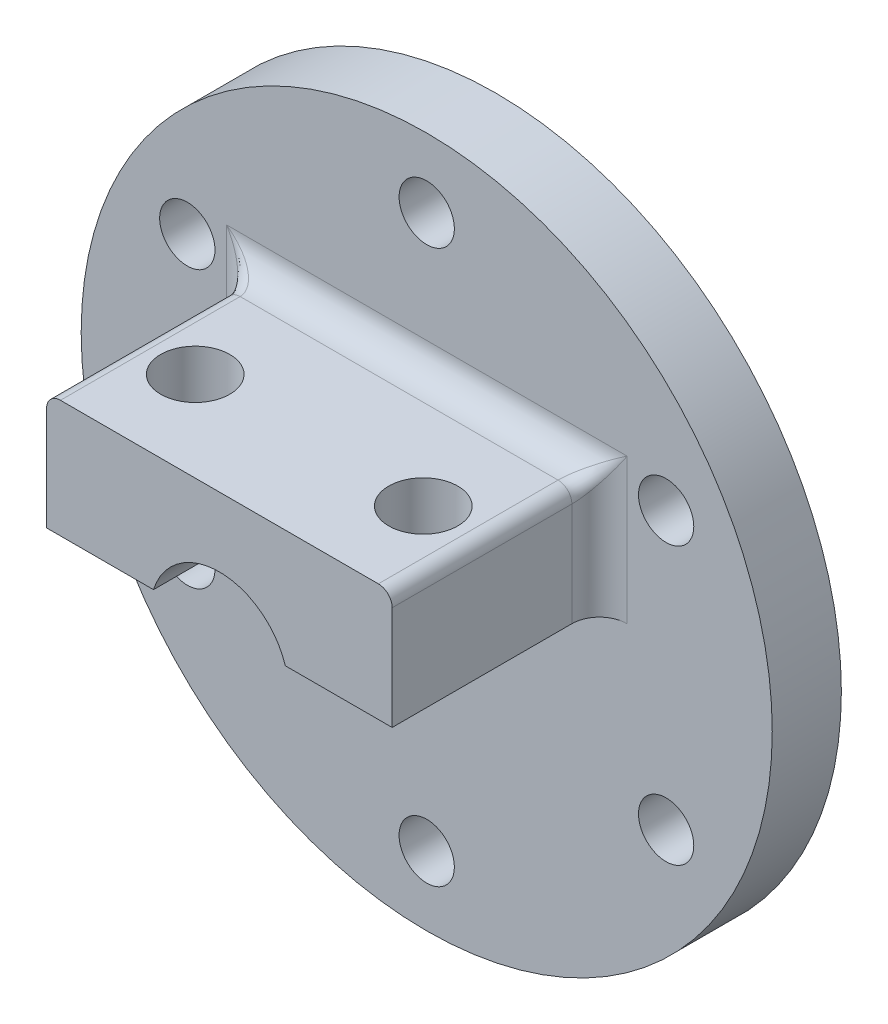
SolidWorks part; units mm, degrees
material "6061 合金"
ref_plane "前视基准面" through (0, 0, 0) normal (0, 0, 1) x (1, 0, 0)
ref_plane "上视基准面" through (0, 0, 0) normal (0, 1, 0) x (1, 0, 0)
ref_plane "右视基准面" through (0, 0, 0) normal (1, 0, 0) x (0, 0, -1)
other "Configuration Table"
sketch "草图2" plane through (0, 0, 0) normal (0, 0, 1) x (1, 0, 0)
  line L0 (0, 0) -> (0, 20)
  line L2 (-3, -4) -> (3, -4)
  circle A0 centre (0, 0) radius 25
  circle A2 centre (0, 20) radius 2
  circle A3 centre (17.3205, 10) radius 2
  circle A4 centre (17.3205, -10) radius 2
  circle A5 centre (0, -20) radius 2
  circle A6 centre (-17.3205, -10) radius 2
  circle A7 centre (-17.3205, 10) radius 2
  arc A8 (3, -4) -> (-3, -4) centre (0, 0) ccw
  point P18 (0, 0)
  dimension "D1" = 50
  dimension "D2" = 6
  dimension "D3" = 20
extrude "凸台-拉伸1" add sketch "草图2" along normal mid plane 5 contours A0 A7 A6 A5 A4 A3 A2 region at (-24.2929, 0, 0)
sketch "草图3" plane through (0, 0, 2.5) normal (0, 0, 1) x (1, 0, 0)
  line L0 (0, 0) -> (0, 10) construction
  line L1 (-12.5, 10) -> (12.5, 10)
  line L2 (-12.5, 10) -> (-12.5, 0)
  line L4 (12.5, 10) -> (12.5, 0)
  line L5 (-5, 0) -> (-12.5, 0)
  line L6 (-12.5, 0) -> (12.5, 0) construction
  line L7 (5, 0) -> (12.5, 0)
  arc A0 (5, 0) -> (-5, 0) centre (0, 0) ccw
  point P0 (0, 0)
  dimension "D1" = 25
  dimension "D2" = 10
extrude "凸台-拉伸2" add sketch "草图3" along normal blind 15
fillet "圆角1" radius 2 3 edges at (12.5, 5, 2.5) (0, 10, 2.5) (-12.5, 5, 2.5)
fillet "圆角2" radius 1 4 edges at (12.5, 10, 11) (-12.5, 10, 11) (13.0858, 10.5858, 3.0858) (-13.0858, 10.5858, 3.0858)
sketch "草图9" plane through (0, 10, 0) normal (0, 1, 0) x (1, 0, 0)
  line L0 (0, -4.5) -> (0, -17.5)
  line L1 (11.5, -4.5) -> (-11.5, -4.5) construction
  line L2 (11.5, -17.5) -> (-11.5, -17.5) construction
  line L3 (0, -11) -> (-8.25, -11)
  circle A0 centre (-8.25, -11) radius 2.5
  circle A1 centre (8.25, -11) radius 2.5
extrude "切除-拉伸2" cut sketch "草图9" against normal blind 10 contours A0 | A1 region at (-10.6793, 10, 11) region at (8.25, 10, 11)
sketch "草图10" plane through (0, 0, 17.5) normal (0, 0, 1) x (1, 0, 0)
  line L1 (0, 1.5) -> (14.5, 1.5)
  line L2 (14.5, 12) -> (14.5, 0) construction
  line L3 (14.5, 1.5) -> (14.5, 0)
  line L4 (14.5, 0) -> (-14.5, 0)
  line L5 (-14.5, 0) -> (-14.5, 1.5)
  line L6 (-14.5, 0) -> (-14.5, 12) construction
  line L7 (-14.5, 1.5) -> (0, 1.5)
extrude "切除-拉伸3" cut sketch "草图10" against normal blind 15
